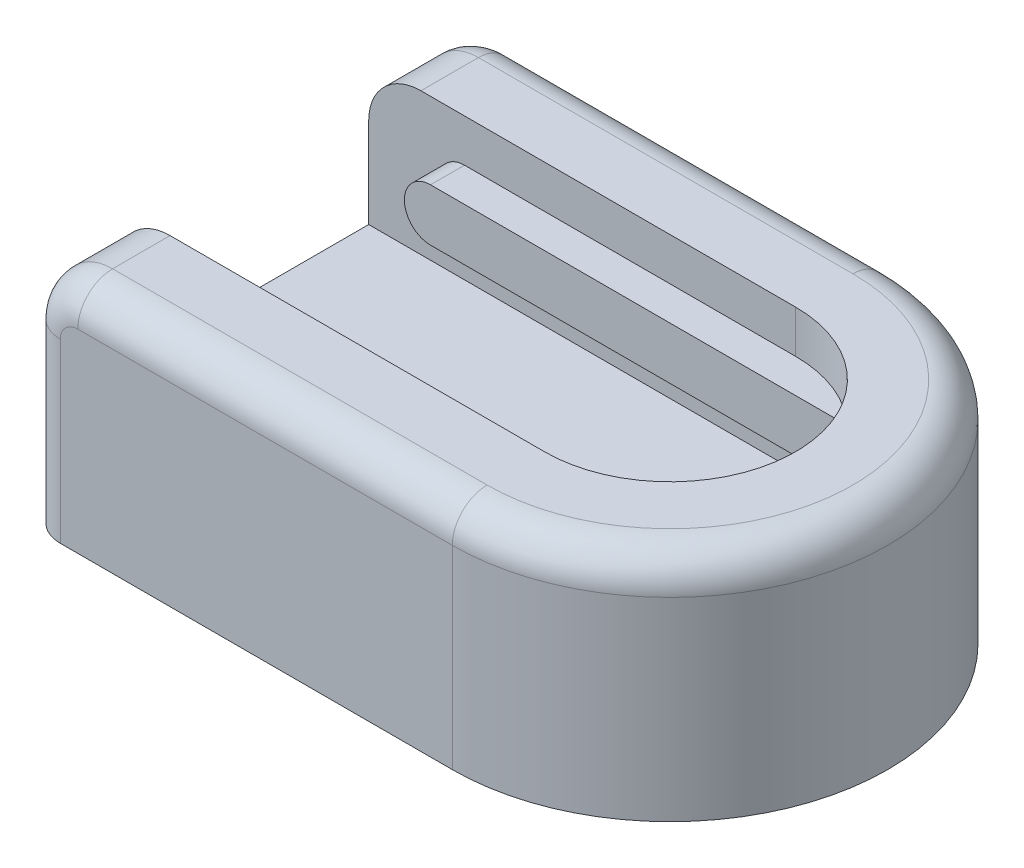
SolidWorks part; units mm, degrees
material "EPDM 60 Durometer"
ref_plane "Front Plane" through (0, 0, 0) normal (0, 0, 1) x (1, 0, 0)
ref_plane "Top Plane" through (0, 0, 0) normal (0, 1, 0) x (1, 0, 0)
ref_plane "Right Plane" through (0, 0, 0) normal (1, 0, 0) x (0, 0, -1)
sketch "Sketch1" plane through (0, 0, 0) normal (0, 1, 0) x (1, 0, 0)
  line L0 (0, 0) -> (24.5, 0)
  line L1 (0, 0) -> (0, 25)
  line L2 (0, 25) -> (24.5, 25)
  arc A0 (24.5, 25) -> (24.5, 0) centre (24.5, 12.5) cw
  point P5 (37, 12.5)
  dimension "D1" = 25
  dimension "D2" = 37
extrude "Boss-Extrude1" add sketch "Sketch1" along normal blind 13.15
sketch "Sketch2" plane through (0, 13.15, 0) normal (0, 1, 0) x (1, 0, 0)
  line L0 (0, 19.7) -> (24.5, 19.7)
  line L1 (0, 25) -> (0, 0) construction
  line L2 (0, 19.7) -> (0, 5.3)
  line L3 (0, 5.3) -> (24.5, 5.3)
  line L4 (0, 25) -> (0, 0)
  arc A0 (24.5, 5.3) -> (24.5, 19.7) centre (24.5, 12.5) ccw
  arc A1 (24.5, 0) -> (24.5, 25) centre (24.5, 12.5) ccw construction
  point P4 (0, 12.5)
  point P7 (0, 12.5)
  point P9 (31.7, 12.5)
  line M3 (0, 25) -> (0, 0)
  dimension "D1" = 14.4
extrude "Cut-Extrude1" cut sketch "Sketch2" against normal blind 8.15 contours L3 A0 L0 M3 region at (15.1203, 13.15, -12.5)
sketch "Sketch3" plane through (0, 5, 0) normal (0, 1, 0) x (1, 0, 0)
  line L0 (0, 5.3) -> (24.5, 5.3) construction
  line L1 (0, 19.7) -> (24.5, 19.7) construction
  line L2 (4, 5.3) -> (24.5, 5.3)
  line L3 (4, 19.7) -> (24.5, 19.7)
  line L6 (29.4272, 17.75) -> (4, 17.75)
  line L7 (-968.5, 12.5) -> (49031.5, 12.5) construction
  line L8 (29.4272, 7.25) -> (4, 7.25)
  line L9 (4, 7.25) -> (4, 5.3)
  line L11 (4, 17.75) -> (4, 19.7)
  arc A0 (24.5, 5.3) -> (24.5, 19.7) centre (24.5, 12.5) ccw construction
  arc A1 (24.5, 5.3) -> (29.4272, 7.25) centre (24.5, 12.5) ccw
  arc A2 (29.4272, 17.75) -> (24.5, 19.7) centre (24.5, 12.5) ccw
  dimension "D1" = 1.95
  dimension "D2" = 4
extrude "Boss-Extrude3" add sketch "Sketch3" along normal blind 3 from offset 2.7
fillet "Fillet1" radius 1.5 4 edges at (4, 7.7, -6.275) (4, 10.7, -6.275) (4, 7.7, -18.725) (4, 10.7, -18.725)
fillet "Fillet2" radius 3 2 edges at (0, 13.15, -22.35) (0, 13.15, -2.65)
fillet "Fillet3" radius 2 7 edges at (0, 5.075, 0) (0.8787, 12.2713, 0) (0, 5.075, -25) (0.8787, 12.2713, -25) (13.75, 13.15, -25) (37, 13.15, -12.5) (13.75, 13.15, 0)
